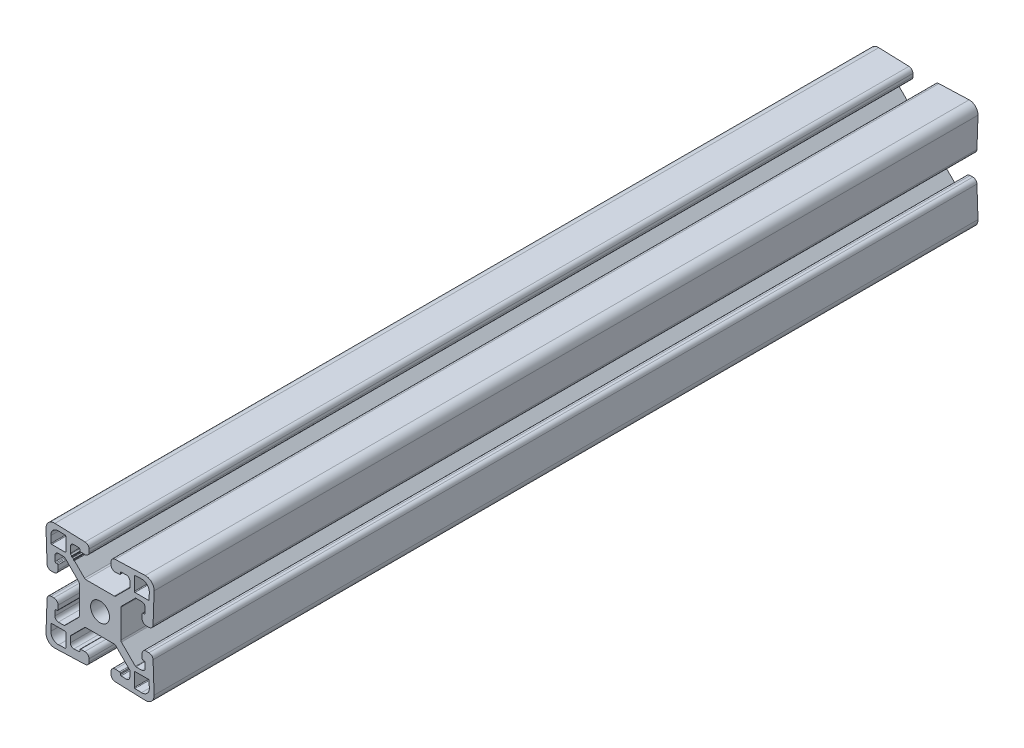
SolidWorks part; units mm, degrees
ref_plane "Front Plane" through (0, 0, 0) normal (0, 0, 1) x (1, 0, 0)
ref_plane "Top Plane" through (0, 0, 0) normal (0, 1, 0) x (1, 0, 0)
ref_plane "Right Plane" through (0, 0, 0) normal (1, 0, 0) x (0, 0, -1)
sketch "Sketch1" plane through (0, 0, 0) normal (0, 0, 1) x (1, 0, 0)
  line L0 (0, 0) -> (0, 20) construction
  line L1 (0, 0) -> (20, 0) construction
  line L2 (0, 0) -> (-20, 20) construction
  line L3 (-16.7142, 19.9981) -> (-5.5358, 19.6077)
  line L4 (-20, 20) -> (0, 20) construction
  line L5 (-4.064, 18.0836) -> (-4.064, 17.069)
  line L6 (-5.6422, 15.5449) -> (-7.1936, 15.5991)
  line L7 (-7.5, 15.9164) -> (-7.5, 16.3198)
  line L8 (-7.8064, 16.6371) -> (-9.6857, 16.7028)
  line L9 (-11, 15.4335) -> (-11, 13.2868)
  line L10 (0, 7.681) -> (-5.2101, 7.681)
  line L11 (-5.7489, 7.9042) -> (-10.907, 13.0623)
  line L12 (-7.9042, 5.7489) -> (-13.0623, 10.907)
  line L13 (-7.681, 0) -> (-7.681, 5.2101)
  line L14 (-15.4335, 11) -> (-13.2868, 11)
  line L15 (-16.6371, 7.8064) -> (-16.7028, 9.6857)
  line L16 (-15.9164, 7.5) -> (-16.3198, 7.5)
  line L17 (-15.5449, 5.6422) -> (-15.5991, 7.1936)
  line L18 (-18.0836, 4.064) -> (-17.069, 4.064)
  line L19 (-19.9981, 16.7142) -> (-19.6077, 5.5358)
  line L20 (-18.2207, 15.3309) -> (-18.1275, 12.661)
  line L21 (-15.3309, 18.2207) -> (-12.661, 18.1275)
  line L22 (-18.1275, 12.661) -> (-12.661, 12.661)
  line L23 (-12.661, 18.1275) -> (-12.661, 12.661)
  line L24 (0, 0) -> (-20, 0) construction
  line L25 (-20, 0) -> (0, 0) construction
  line L26 (0, 0) -> (0, -20) construction
  line L27 (-20, -20) -> (-20, 20) construction
  line L28 (0, 20) -> (20, 20) construction
  line L30 (-20, -20) -> (20, -20) construction
  arc A0 (-19.9981, 16.7142) -> (-16.7142, 19.9981) centre (-16.825, 16.825) cw
  arc A1 (-7.1936, 15.5991) -> (-7.5, 15.9164) centre (-7.1825, 15.9164) cw
  arc A2 (-7.5, 16.3198) -> (-7.8064, 16.6371) centre (-7.8175, 16.3198) ccw
  arc A3 (-9.6857, 16.7028) -> (-11, 15.4335) centre (-9.73, 15.4335) ccw
  arc A4 (-4.064, 17.069) -> (-5.6422, 15.5449) centre (-5.589, 17.069) cw
  arc A5 (-5.5358, 19.6077) -> (-4.064, 18.0836) centre (-5.589, 18.0836) cw
  arc A6 (-5.2101, 7.681) -> (-5.7489, 7.9042) centre (-5.2101, 8.443) cw
  arc A7 (-7.9042, 5.7489) -> (-7.681, 5.2101) centre (-8.443, 5.2101) cw
  arc A8 (-11, 13.2868) -> (-10.907, 13.0623) centre (-10.6825, 13.2868) ccw
  arc A9 (-18.0836, 4.064) -> (-19.6077, 5.5358) centre (-18.0836, 5.589) cw
  arc A10 (-15.5449, 5.6422) -> (-17.069, 4.064) centre (-17.069, 5.589) cw
  arc A11 (-15.9164, 7.5) -> (-15.5991, 7.1936) centre (-15.9164, 7.1825) cw
  arc A12 (-16.6371, 7.8064) -> (-16.3198, 7.5) centre (-16.3198, 7.8175) ccw
  arc A13 (-15.4335, 11) -> (-16.7028, 9.6857) centre (-15.4335, 9.73) ccw
  arc A14 (-13.0623, 10.907) -> (-13.2868, 11) centre (-13.2868, 10.6825) ccw
  arc A15 (-15.3309, 18.2207) -> (-18.2207, 15.3309) centre (-15.4284, 15.4284) ccw
  circle A16 centre (0, 0) radius 3.5
  point P26 (-7.5, 15.6098)
  point P29 (-7.5, 16.6264)
  point P32 (-11, 16.7487)
  point P35 (-4.064, 15.4898)
  point P38 (-4.064, 19.5563)
  point P42 (-5.5257, 7.681)
  point P45 (-7.681, 5.5257)
  point P48 (-11, 13.1553)
  point P51 (-19.5563, 4.064)
  point P54 (-15.4898, 4.064)
  point P57 (-15.6098, 7.5)
  point P60 (-16.6264, 7.5)
  point P63 (-16.7487, 11)
  point P66 (-13.1553, 11)
  point P80 (-20, 0)
  point P85 (0, -20)
  point P88 (0, -20)
  dimension "D11" = 3.175
  dimension "D14" = 1.27
  dimension "D16" = 1.525
  dimension "D15" = 0.762
  dimension "D21" = 2.794
  dimension "D4" = 0.3175
  dimension "Center Hole Diameter" = 7
  dimension "D1" = 45
  dimension "D2" = 2
  dimension "Rail Width" = 40
  dimension "T-Slot Width" = 8.128
  dimension "D6" = 3.048
  dimension "D10" = 3.048
  dimension "D13" = 1.728
  dimension "D8" = 22
  dimension "D18" = 1.661
  dimension "D19" = 7.339
  dimension "D20" = 7.339
  dimension "T-Slot Depth" = 12.319
  dimension "D9" = 4.064
  dimension "Rail Height1" = 40
  dimension "Rail Height" = 40
  dimension "D23" = 15.362
  dimension "D3" = 20
  dimension "D7" = 3.5
sketch "Sketch2" plane through (0, 0, 0) normal (1, 0, 0) x (0, 0, -1)
  line L0 (-152.4, 0) -> (152.4, 0)
  line L1 (-152.4, -20) -> (-152.4, 20) construction
  line L2 (0, 0) -> (0, 20) construction
  line L3 (0, 0) -> (0, 20) construction
  line L4 (152.4, -20) -> (152.4, 20) construction
  point P0 (-92.4, 0)
  point P3 (0, 0)
  point P7 (92.4, 0)
  point P11 (-152.4, 0)
  point P14 (152.4, 0)
  dimension "D1" = 60
  dimension "Length" = 304.8
sketch "Sketch3" plane through (0, 0, 0) normal (0, 0, 1) x (1, 0, 0)
  line L0 (-7.681, 0) -> (-7.681, 5.2101) construction
  line L1 (-7.9042, 5.7489) -> (-13.0623, 10.907) construction
  line L2 (-15.4335, 11) -> (-13.2868, 11) construction
  line L3 (-16.6371, 7.8064) -> (-16.7028, 9.6857) construction
  line L4 (-18.2207, 15.3309) -> (-18.1275, 12.661)
  line L5 (-18.1275, 12.661) -> (-12.661, 12.661)
  line L6 (-12.661, 12.661) -> (-12.661, 18.1275)
  line L7 (-12.661, 18.1275) -> (-15.3309, 18.2207)
  line L8 (-18.2207, 15.3309) -> (-18.136, 12.9061)
  line L9 (-17.8822, 12.661) -> (-12.915, 12.661)
  line L10 (-12.661, 12.915) -> (-12.661, 17.8822)
  line L11 (-12.9061, 18.136) -> (-15.3309, 18.2207)
  line L12 (-15.9164, 7.5) -> (-16.3198, 7.5) construction
  line L13 (-15.5449, 5.6422) -> (-15.5991, 7.1936) construction
  line L14 (-18.0836, 4.064) -> (-17.069, 4.064) construction
  line L15 (-19.9981, 16.7142) -> (-19.6077, 5.5358) construction
  line L16 (-16.7142, 19.9981) -> (-5.5358, 19.6077) construction
  line L17 (-4.064, 18.0836) -> (-4.064, 17.069) construction
  line L18 (-5.6422, 15.5449) -> (-7.1936, 15.5991) construction
  line L19 (-7.5, 15.9164) -> (-7.5, 16.3198) construction
  line L20 (-7.8064, 16.6371) -> (-9.6857, 16.7028) construction
  line L21 (-11, 15.4335) -> (-11, 13.2868) construction
  line L22 (-5.7489, 7.9042) -> (-10.907, 13.0623) construction
  line L23 (0, 7.681) -> (-5.2101, 7.681) construction
  line L24 (-7.681, 0) -> (-7.681, 5.2101)
  line L25 (-7.9042, 5.7489) -> (-13.0623, 10.907)
  line L26 (-15.4335, 11) -> (-13.2868, 11)
  line L27 (-16.6371, 7.8064) -> (-16.7028, 9.6857)
  line L28 (-15.9164, 7.5) -> (-16.3198, 7.5)
  line L29 (-15.5449, 5.6422) -> (-15.5991, 7.1936)
  line L30 (-18.0836, 4.064) -> (-17.069, 4.064)
  line L31 (-19.9981, 16.7142) -> (-19.6077, 5.5358)
  line L32 (-16.7142, 19.9981) -> (-5.5358, 19.6077)
  line L33 (-4.064, 18.0836) -> (-4.064, 17.069)
  line L34 (-5.6422, 15.5449) -> (-7.1936, 15.5991)
  line L35 (-7.5, 15.9164) -> (-7.5, 16.3198)
  line L36 (-7.8064, 16.6371) -> (-9.6857, 16.7028)
  line L37 (-11, 15.4335) -> (-11, 13.2868)
  line L38 (-5.7489, 7.9042) -> (-10.907, 13.0623)
  line L39 (0, 7.681) -> (-5.2101, 7.681)
  line L40 (-7.681, 0) -> (-3.5, 0)
  line L41 (0, 3.5) -> (0, 7.681)
  arc A0 (-7.681, 5.2101) -> (-7.9042, 5.7489) centre (-8.443, 5.2101) ccw construction
  circle A1 centre (0, 0) radius 3.5
  arc A2 (0, 3.5) -> (-3.5, 0) centre (0, 0) ccw
  arc A3 (-15.3309, 18.2207) -> (-18.2207, 15.3309) centre (-15.4284, 15.4284) ccw
  arc A4 (-15.3309, 18.2207) -> (-18.2207, 15.3309) centre (-15.4284, 15.4284) ccw
  arc A5 (-13.0623, 10.907) -> (-13.2868, 11) centre (-13.2868, 10.6825) ccw construction
  arc A6 (-15.4335, 11) -> (-16.7028, 9.6857) centre (-15.4335, 9.73) ccw construction
  arc A7 (-16.6371, 7.8064) -> (-16.3198, 7.5) centre (-16.3198, 7.8175) ccw construction
  arc A8 (-15.5991, 7.1936) -> (-15.9164, 7.5) centre (-15.9164, 7.1825) ccw construction
  arc A9 (-17.069, 4.064) -> (-15.5449, 5.6422) centre (-17.069, 5.589) ccw construction
  arc A10 (-19.6077, 5.5358) -> (-18.0836, 4.064) centre (-18.0836, 5.589) ccw construction
  arc A11 (-16.7142, 19.9981) -> (-19.9981, 16.7142) centre (-16.825, 16.825) ccw construction
  arc A12 (-4.064, 18.0836) -> (-5.5358, 19.6077) centre (-5.589, 18.0836) ccw construction
  arc A13 (-5.6422, 15.5449) -> (-4.064, 17.069) centre (-5.589, 17.069) ccw construction
  arc A14 (-7.5, 15.9164) -> (-7.1936, 15.5991) centre (-7.1825, 15.9164) ccw construction
  arc A15 (-7.5, 16.3198) -> (-7.8064, 16.6371) centre (-7.8175, 16.3198) ccw construction
  arc A16 (-9.6857, 16.7028) -> (-11, 15.4335) centre (-9.73, 15.4335) ccw construction
  arc A17 (-11, 13.2868) -> (-10.907, 13.0623) centre (-10.6825, 13.2868) ccw construction
  arc A18 (-5.7489, 7.9042) -> (-5.2101, 7.681) centre (-5.2101, 8.443) ccw construction
  arc A19 (-7.681, 5.2101) -> (-7.9042, 5.7489) centre (-8.443, 5.2101) ccw
  arc A20 (-13.0623, 10.907) -> (-13.2868, 11) centre (-13.2868, 10.6825) ccw
  arc A21 (-15.4335, 11) -> (-16.7028, 9.6857) centre (-15.4335, 9.73) ccw
  arc A22 (-16.6371, 7.8064) -> (-16.3198, 7.5) centre (-16.3198, 7.8175) ccw
  arc A23 (-15.5991, 7.1936) -> (-15.9164, 7.5) centre (-15.9164, 7.1825) ccw
  arc A24 (-17.069, 4.064) -> (-15.5449, 5.6422) centre (-17.069, 5.589) ccw
  arc A25 (-19.6077, 5.5358) -> (-18.0836, 4.064) centre (-18.0836, 5.589) ccw
  arc A26 (-16.7142, 19.9981) -> (-19.9981, 16.7142) centre (-16.825, 16.825) ccw
  arc A27 (-4.064, 18.0836) -> (-5.5358, 19.6077) centre (-5.589, 18.0836) ccw
  arc A28 (-5.6422, 15.5449) -> (-4.064, 17.069) centre (-5.589, 17.069) ccw
  arc A29 (-7.5, 15.9164) -> (-7.1936, 15.5991) centre (-7.1825, 15.9164) ccw
  arc A30 (-7.5, 16.3198) -> (-7.8064, 16.6371) centre (-7.8175, 16.3198) ccw
  arc A31 (-9.6857, 16.7028) -> (-11, 15.4335) centre (-9.73, 15.4335) ccw
  arc A32 (-11, 13.2868) -> (-10.907, 13.0623) centre (-10.6825, 13.2868) ccw
  arc A33 (-5.7489, 7.9042) -> (-5.2101, 7.681) centre (-5.2101, 8.443) ccw
  arc A36 (-12.661, 17.8822) -> (-12.9061, 18.136) centre (-12.915, 17.8822) ccw
  arc A37 (-12.915, 12.661) -> (-12.661, 12.915) centre (-12.915, 12.915) ccw
  arc A38 (-18.136, 12.9061) -> (-17.8822, 12.661) centre (-17.8822, 12.915) ccw
  dimension "D3" = 0.254
  dimension "D1" = 0
  dimension "D2" = 0
extrude "Boss-Extrude1" add sketch "Sketch3" along normal mid plane 304.8
pattern_circular "CirPattern1" count 4 over 360 about axis through (0, 0, 152.4) along (0, 0, -1) of "Boss-Extrude1"
sketch "Sketch4" plane through (0, 0, 0) normal (0, 0, 1) x (1, 0, 0)
  line L1 (-10.5057, 12.661) -> (-9.5057, 12.661)
  line L8 (-5.7489, 7.9042) -> (-10.907, 13.0623) construction
  line L9 (-9.5057, 12.661) -> (-9.5057, 11.661)
  line L10 (-9.5057, 11.661) -> (-9.8391, 11.661)
  line L12 (-10.1724, 12.3277) -> (-9.8391, 11.9943)
  line L20 (-9.8391, 11.9943) -> (-9.8391, 12.3277) construction
  line L22 (-9.8391, 11.661) -> (-9.8391, 11.9943)
  line L23 (-9.8391, 12.3277) -> (-10.1724, 12.3277) construction
  line L25 (-10.1724, 12.3277) -> (-10.5057, 12.3277)
  line L26 (-10.5057, 12.3277) -> (-10.5057, 12.661)
  line L27 (-17.8822, 12.661) -> (-12.915, 12.661) construction
  dimension "D2" = 1
extrude "Cut-Extrude1" cut sketch "Sketch4" against normal through all both and the other way through all
ref_plane "Contact Plane 1" through (0, 20, 0) normal (0, 1, 0) x (1, 0, 0)
ref_plane "Contact Plane 2" through (20, 0, 0) normal (1, 0, 0) x (0, 0, -1)
ref_plane "Contact Plane 3" through (0, -20, 0) normal (0, -1, 0) x (-1, 0, 0)
ref_plane "Contact Plane 4" through (-20, 0, 0) normal (-1, 0, 0) x (0, 0, 1)
equation "\"D1@Sketch2\"=\"Rail Width@Sketch1\"*1.5"
equation "\"D1@Boss-Extrude1\"=\"Length@Sketch2\""
equation "\"ShaftDiameter\"= 12mm"
equation "\"PendulumDiameter\"=12mm"
equation "\"PendulumLength\"= 140mm"
equation "\"EncoderOuterDiameter\"=1.5"
equation "\"EncoderShaftDiameter\"= 6mm"
equation "\"EncoderShaftLength\"=15mm+.5in+3mm"
equation "\"PendulumHolderangle\"=60"
equation "\"PendulumholderBottomHeight\"= 75"
equation "\"PendulumholderBottomWidth\"= 75"
equation "\"PendulumholderHeight\"=25"
equation "\"BearingOutsideDiameter\"=21mm"
equation "\"PendulumHolderWidth\"= 100mm"
equation "\"ShaftHeightFromTSlot\"= 100mm"
equation "\"BearingThickness\"= 5mm"
equation "\"SlipRingOuterDiameter\"=56mm"
equation "\"SlipringBigThickness\"=25mm"
equation "\"SlipringSmallThickness\"=8.5mm"
equation "\"Tol\"=2mm"
equation "\"ScrewHole\"= 5mm"
equation "\"Tframwidth\"= 40mm"
equation "\"TFrameheight\"= 12in"
equation "\"Length@Sketch2\"=\"TFrameheight\""
